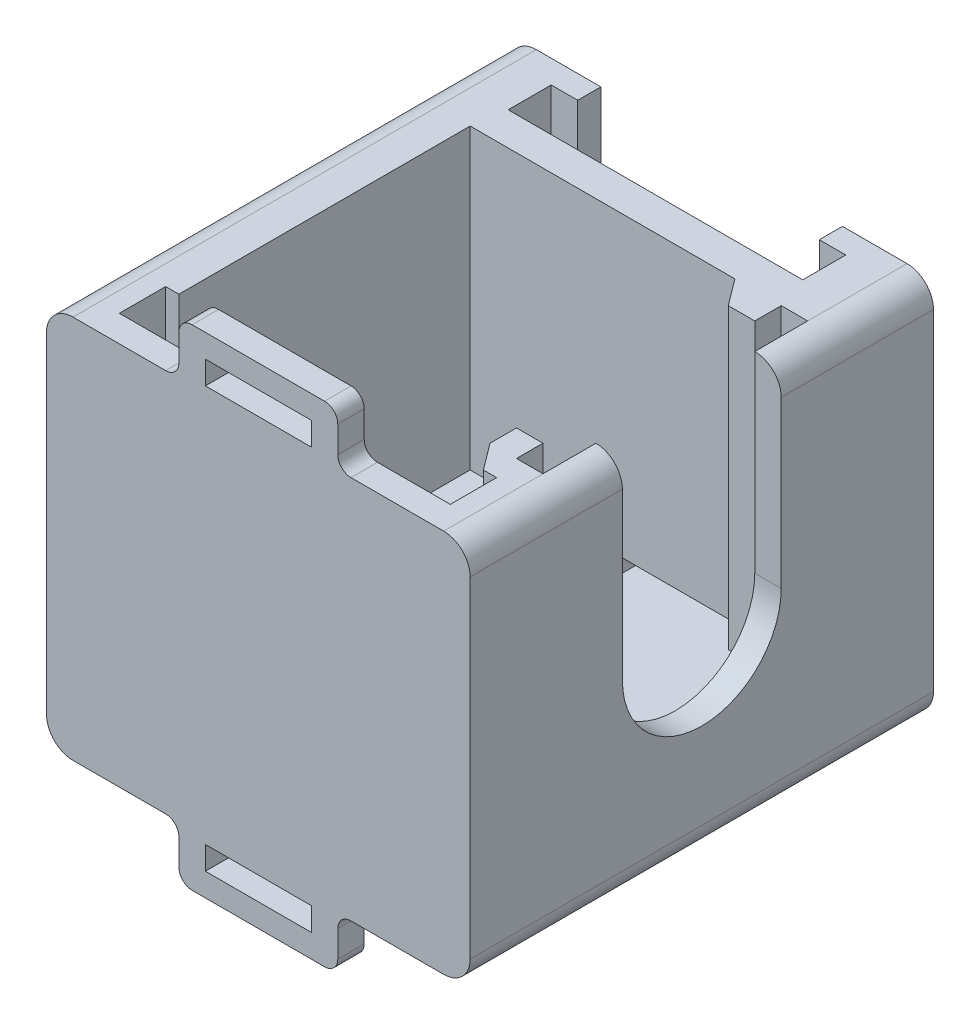
SolidWorks part; units mm, degrees
material "UNOBTANIUM"
ref_plane "Top Plane" through (0, 0, 0) normal (0, 0, 1) x (1, 0, 0)
ref_plane "Right Plane" through (0, 0, 0) normal (0, 1, 0) x (1, 0, 0)
ref_plane "Front Plane" through (0, 0, 0) normal (1, 0, 0) x (0, 0, -1)
ref_axis "x-axis" through (-17.6, 0, 0) along (1, 0, 0)
ref_axis "y-axis" through (0, -14.85, 0) along (0, 1, 0)
ref_axis "z-axis" through (0, 0, 36.75) along (0, 0, -1)
sketch "Sketch1" plane through (0, 0, 0) normal (0, 0, 1) x (1, 0, 0)
  line L1 (-16, 14.5) -> (16, 14.5)
  line L2 (-16, 14.5) -> (-16, -14.5)
  line L3 (-16, -14.5) -> (16, -14.5)
  line L4 (16, 14.5) -> (16, -14.5)
  line L5 (-16, 14.5) -> (16, -14.5) construction
  line L6 (-16, -14.5) -> (16, 14.5) construction
  point P0 (0, 0)
  dimension "D1" = 32
  dimension "D2" = 29
extrude "Boss-Extrude1" add sketch "Sketch1" along normal blind 35
fillet "Fillet1" radius 2 4 edges at (16, -14.5, 17.5) (16, 14.5, 17.5) (-16, -14.5, 17.5) (-16, 14.5, 17.5)
sketch "Sketch2" plane through (0, -14.5, 0) normal (0, -1, 0) x (1, 0, 0)
  line L0 (-9.125, 0) -> (-9.125, 1.75)
  line L1 (-14, 0) -> (14, 0) construction
  line L2 (-9.125, 1.75) -> (-11.125, 1.75)
  line L3 (-11.125, 1.75) -> (-11.125, 5)
  line L4 (-11.125, 5) -> (11.125, 5)
  line L5 (11.125, 5) -> (11.125, 1.75)
  line L6 (11.125, 1.75) -> (9.125, 1.75)
  line L7 (9.125, 1.75) -> (9.125, 0)
  line L9 (-9.125, 0) -> (9.125, 0)
  point P4 (0, 0)
  dimension "D1" = 18.25
  dimension "D2" = 1.75
  dimension "D3" = 3.25
  dimension "D4" = 22.25
extrude "Slot for Coil" cut sketch "Sketch2" against normal through all both and the other way through all
sketch "Sketch3" plane through (0, -14.5, 0) normal (0, -1, 0) x (1, 0, 0)
  line L0 (-9.125, 0) -> (-9.125, 1.75)
  line L1 (-9.125, 1.75) -> (-11.125, 1.75)
  line L2 (-11.125, 1.75) -> (-11.125, 5)
  line L3 (-11.125, 5) -> (11.125, 5)
  line L4 (11.125, 5) -> (11.125, 1.75)
  line L5 (11.125, 1.75) -> (9.125, 1.75)
  line L6 (9.125, 1.75) -> (9.125, 0)
  line L7 (9.125, 0) -> (-9.125, 0)
extrude "Boss-Extrude2" add sketch "Sketch3" against normal blind 6.5
sketch "Sketch4" plane through (0, 0, 1.75) normal (0, 0, -1) x (-1, 0, 0)
  line L1 (-9.125, 7.5) -> (-9.125, 6.5)
  line L2 (-9.125, 14.5) -> (-9.125, -8) construction
  arc A0 (-9.125, 7.5) -> (-9.125, 6.5) centre (-9.5, 7) cw
  dimension "D1" = 0.625
  dimension "D2" = 0.25
  dimension "D3" = 7
extrude "Boss-Extrude3" add sketch "Sketch4" along normal up to surface (1.75 mm away) up to face at (0, 1.0833, 0)
mirror "Mirror1" about plane through (0, 0, 0) normal (1, 0, 0) of "Boss-Extrude3"
sketch "Sketch5" plane through (0, 0, 0) normal (0, 0, -1) x (-1, 0, 0)
  line L0 (9.125, -8) -> (-9.125, -8) construction
  line L1 (-1, -8) -> (1, -8)
  line L2 (-1, -8) -> (-1, -14.5)
  line L3 (-1, -14.5) -> (1, -14.5)
  line L4 (1, -8) -> (1, -14.5)
  line L5 (14, -14.5) -> (-14, -14.5) construction
  point P8 (0, -8)
  dimension "D1" = 2
extrude "slot to feed in wire" cut sketch "Sketch5" against normal offset from surface (33 mm away) 2 up to face at (0, 0, 35)
sketch "Sketch6" plane through (0, 14.5, 0) normal (0, 1, 0) x (1, 0, 0)
  line L7 (11.5, -7.5) -> (-11.5, -7.5)
  line L8 (11.125, -5) -> (-11.125, -5) construction
  line L9 (0, -7.5) -> (0, -5) construction
  line L12 (-12.5, -33) -> (-12.5, -29.5)
  line L13 (-12.5, -29.5) -> (-11.5, -29.5)
  line L14 (-11.5, -29.5) -> (-11.5, -7.5)
  line L16 (12.5, -33) -> (12.5, -29.5)
  line L17 (12.5, -29.5) -> (11.5, -29.5)
  line L18 (11.5, -29.5) -> (11.5, -7.5)
  line L19 (-12.5, -33) -> (12.5, -33)
  line L20 (14, -35) -> (-14, -35) construction
  dimension "D1" = 2.5
  dimension "D2" = 3.5
  dimension "D3" = 1
  dimension "D4" = 23
  dimension "D5" = 2
  dimension "D6" = 3.5
  dimension "D7" = 1
extrude "slot fo PCB" cut sketch "Sketch6" against normal up to surface (22.5 mm away) up to face at (7.0833, -8, 2.25)
sketch "Sketch7" plane through (0, -14.5, 0) normal (0, -1, 0) x (1, 0, 0)
  line L0 (1, 0) -> (14, 0) construction
  line L1 (1, 0) -> (-1, 0)
  line L2 (1, 0) -> (1, 33)
  line L3 (1, 33) -> (-1, 33)
  line L4 (-1, 0) -> (-1, 33)
  line L5 (1, 33) -> (1, 0) construction
extrude "Boss-Extrude4" add sketch "Sketch7" against normal offset from surface (2.5 mm away) 4 up to face at (7.0833, -8, 2.25)
fillet "Fillet2" radius 6 1 edges at (0, -12, 33)
ref_axis "Axis1" through (63.07, 0, 17.75) along (-1, 0, 0)
ref_plane "Plane1" through (0, 0, 17.75) normal (0, 0, -1) x (-1, 0, 0)
sketch "Sketch11" plane through (16, 0, 44) normal (1, 0, 0) x (0, 0, -1)
  line L0 (26.5, 25) -> (26.5, 0) construction
  line L4 (32.5, 25) -> (32.5, 0)
  line L5 (20.5, 25) -> (20.5, 0)
  line L6 (9, 12.5) -> (44, 12.5) construction
  line L7 (26.5, 0) -> (44, 0) construction
  line L8 (9, 12.5) -> (9, -12.5) construction
  arc A2 (32.5, 25) -> (20.5, 25) centre (26.5, 25) ccw
  arc A3 (20.5, 0) -> (32.5, 0) centre (26.5, 0) ccw
  point P2 (26.5, 12.5)
  dimension "D1" = 12
  dimension "D2" = 17.5
extrude "Rod Mount Slot" cut sketch "Sketch11" against normal up to next
sketch "Sketch14" plane through (0, 14.5, 0) normal (0, 1, 0) x (1, 0, 0)
  line L7 (14, -35) -> (14, -23.5) construction
  line L8 (11.5, -7.5) -> (14, -7.5)
  line L9 (11.5, -7.5) -> (11.5, -27.5)
  line L10 (11.5, -27.5) -> (14, -27.5)
  line L11 (14, -7.5) -> (14, -27.5)
  line L13 (12.5, -29.5) -> (11.5, -29.5) construction
  dimension "D2" = 2
extrude "Side cavity for mount plate" cut sketch "Sketch14" against normal up to surface (22.5 mm away) up to face at (-8.3333, -8, 23.219)
sketch "Sketch16" plane through (0, 14.5, 0) normal (0, 1, 0) x (1, 0, 0)
  line L0 (1, -7.5) -> (14, -7.5) construction
  line L12 (12, -7.5) -> (10, -7.5)
  line L15 (12, -7.5) -> (12, -9.5)
  line L16 (12, -9.5) -> (10, -9.5)
  line L17 (10, -7.5) -> (10, -9.5)
  line L18 (14, -11.5) -> (14, -7.5) construction
  line L19 (14, -27.5) -> (11.5, -27.5) construction
  line L20 (12, -27.5) -> (10, -27.5)
  line L21 (12, -27.5) -> (12, -25.5)
  line L22 (12, -25.5) -> (10, -25.5)
  line L23 (10, -27.5) -> (10, -25.5)
  line L24 (14, -27.5) -> (14, -23.5) construction
  line L25 (14, -7.5) -> (14, -27.5) construction
  dimension "D6" = 2
  dimension "D7" = 2
  dimension "D8" = 2
  dimension "D9" = 2
  dimension "D10" = 4
extrude "Side stops for mount plate" add sketch "Sketch16" against normal up to surface (22.5 mm away) up to face at (-8.3333, -8, 23.219)
sketch "Sketch20" plane through (0, 14.5, 0) normal (0, 1, 0) x (1, 0, 0)
  line L7 (11.5, -29.5) -> (10, -27.5)
  line L8 (10, -27.5) -> (11.5, -27.5)
  line L9 (11.5, -27.5) -> (11.5, -29.5)
  line L10 (10, -9.5) -> (8.5, -7.5)
  line L11 (10, -7.5) -> (-11.5, -7.5) construction
  line L12 (8.5, -7.5) -> (10, -7.5)
  line L13 (10, -7.5) -> (10, -9.5)
extrude "Boss-Extrude6" add sketch "Sketch20" against normal up to surface (22.5 mm away) up to face at (-8.3333, -8, 23.219)
sketch "Sketch21" plane through (0, 14.5, 0) normal (0, 1, 0) x (-1, 0, 0)
  line L0 (0, 0) -> (0, 35) construction
  line L1 (-14, 35) -> (14, 35) construction
  line L2 (12.5, 33) -> (-12.5, 33) construction
  line L3 (-6, 35) -> (6, 35)
  line L4 (-6, 35) -> (-6, 33)
  line L5 (-6, 33) -> (6, 33)
  line L6 (6, 35) -> (6, 33)
  point P12 (0, 35)
  dimension "D1" = 12
extrude "Boss-Extrude7" add sketch "Sketch21" along normal blind 4
sketch "Sketch23" plane through (0, 0, 35) normal (0, 0, 1) x (1, 0, 0)
  line L0 (0, 0) -> (0, 18.5) construction
  line L1 (-6, 14.5) -> (-14, 14.5) construction
  line L3 (-4, 16.75) -> (4, 16.75)
  line L4 (-4, 16.75) -> (-4, 15)
  line L5 (-4, 15) -> (4, 15)
  line L6 (4, 16.75) -> (4, 15)
  line L7 (-6, 18.5) -> (6, 18.5) construction
  point P3 (0, 16.75)
  dimension "D1" = 1.75
  dimension "D2" = 8
  dimension "D3" = 0.5
extrude "Cut-Extrude7" cut sketch "Sketch23" against normal up to next
mirror "Mirror3" about plane through (0, 0, 0) normal (0, 1, 0) of "Boss-Extrude7", "Cut-Extrude7"
fillet "Fillet3" radius 1 8 edges at (-6, 14.5, 34) (6, 14.5, 34) (6, 18.5, 34) (-6, 18.5, 34) (6, -14.5, 34) (-6, -14.5, 34) (6, -18.5, 34) (-6, -18.5, 34)
sketch "Sketch26" plane through (-16, 0, 0) normal (1, 0, 0) x (0, 0, -1)
  circle A0 centre (-23.015, -2.89) radius 5.25
  dimension "D1" = 10.5
extrude "Cut-Extrude8" cut sketch "Sketch26" along normal up to next
